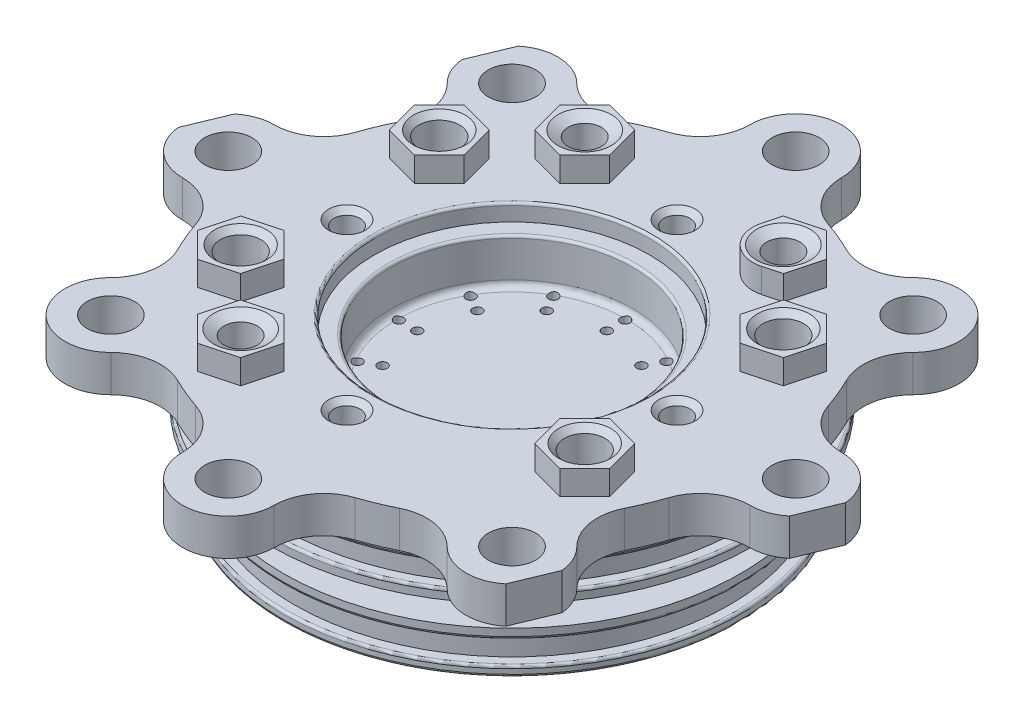
SolidWorks part; units mm, degrees
material "6061-T6 (SS)"
ref_plane "Front Plane" through (0, 0, 0) normal (0, 0, 1) x (1, 0, 0)
ref_plane "Top Plane" through (0, 0, 0) normal (0, 1, 0) x (1, 0, 0)
ref_plane "Right Plane" through (0, 0, 0) normal (1, 0, 0) x (0, 0, -1)
sketch "Sketch1" plane through (0, 0, 0) normal (0, 0, 1) x (1, 0, 0)
  line L0 (0, 2.032) -> (0, 18.8976)
  line L1 (0, 18.8976) -> (25.1206, 18.8976)
  line L2 (25.1206, 18.8976) -> (25.1206, 28.1432)
  line L3 (28.575, 31.5976) -> (69.85, 31.5976)
  line L4 (69.85, 31.5976) -> (69.85, 23.9776)
  line L5 (69.85, 23.9776) -> (50.248, 23.9776)
  line L6 (50.248, 23.9776) -> (50.248, 21.9456)
  line L7 (50.248, 21.9456) -> (47.962, 21.9456)
  line L8 (47.962, 21.9456) -> (47.962, 17.1958)
  line L9 (47.962, 17.1958) -> (50.248, 17.1958)
  line L10 (50.248, 17.1958) -> (50.248, 15.1638)
  line L11 (50.248, 15.1638) -> (38.1, 15.1638)
  line L12 (38.1, 15.1638) -> (38.1, 8.8138)
  line L13 (38.1, 8.8138) -> (47.498, 8.8138)
  line L14 (47.498, 8.8138) -> (47.498, 6.7818)
  line L15 (47.498, 6.7818) -> (45.212, 6.7818)
  line L16 (45.212, 6.7818) -> (45.212, 2.032)
  line L17 (45.212, 2.032) -> (47.498, 2.032)
  line L18 (47.498, 2.032) -> (47.498, 0)
  line L19 (47.498, 0) -> (44.069, 0)
  line L20 (44.069, 0) -> (42.037, 2.032)
  line L21 (42.037, 2.032) -> (0, 2.032)
  line L22 (28.575, 31.5976) -> (28.575, 28.1432)
  line L23 (28.575, 28.1432) -> (25.1206, 28.1432)
  dimension "D1" = 2.032
  dimension "D2" = 2.032
  dimension "D3" = 2.032
  dimension "D4" = 2.032
  dimension "D5" = 2.286
  dimension "D6" = 2.286
  dimension "D7" = 4.7498
  dimension "D8" = 4.7498
  dimension "D9" = 47.498
  dimension "D10" = 6.35
  dimension "D11" = 7.62
  dimension "D12" = 3.4544
  dimension "D13" = 28.575
  dimension "D14" = 45
  dimension "D15" = 3.429
  dimension "D16" = 38.1
  dimension "D17" = 69.85
  dimension "D18" = 50.248
  dimension "D19" = 3.4544
  dimension "D20" = 12.7
revolve "Revolve1" add sketch "Sketch1" angle 360 about L0
fillet "Fillet1" radius 0.508 5 edges at (0, 21.9456, -50.248) (0, 17.1958, -50.248) (0, 6.7818, -47.498) (0, 0, -47.498) (0, 2.032, -47.498)
fillet "Fillet2" radius 0.508 5 edges at (0, 0, -44.069) (0, 2.032, -42.037) (0, 8.8138, -38.1) (0, 15.1638, -38.1) (0, 23.9776, -50.248)
fillet "Fillet3" radius 1.27 1 edges at (0, 18.8976, -25.1206)
fillet "Fillet4" radius 0.508 2 edges at (0, 28.1432, -25.1206) (0, 31.5976, -28.575)
sketch "Sketch3" plane through (0, 0, 0) normal (0, 1, 0) x (1, 0, 0)
  arc A0 (-46.4668, 23.062) -> (-49.1643, 16.5497) centre (0, 0) ccw
  circle A1 centre (0, 0) radius 58.9409 construction
  arc A2 (9.525, 58.9409) -> (-9.525, 58.9409) centre (0, 58.9409) ccw
  circle A3 centre (0, 58.9409) radius 4.9022
  arc A4 (9.525, 58.9409) -> (16.5497, 49.1643) centre (19.8407, 58.9409) ccw
  arc A5 (-9.525, 58.9409) -> (-16.5497, 49.1643) centre (-19.8407, 58.9409) cw
  arc A8 (34.9423, 48.4127) -> (23.062, 46.4668) centre (27.648, 55.707) cw
  arc A9 (48.4127, 34.9423) -> (34.9423, 48.4127) centre (41.6775, 41.6775) ccw
  circle A10 centre (41.6775, 41.6775) radius 4.9022
  arc A11 (48.4127, 34.9423) -> (46.4668, 23.062) centre (55.707, 27.648) ccw
  arc A12 (58.9409, 9.525) -> (49.1643, 16.5497) centre (58.9409, 19.8407) cw
  arc A13 (58.9409, -9.525) -> (58.9409, 9.525) centre (58.9409, 0) ccw
  circle A14 centre (58.9409, 0) radius 4.9022
  arc A15 (58.9409, -9.525) -> (49.1643, -16.5497) centre (58.9409, -19.8407) ccw
  arc A16 (48.4127, -34.9423) -> (46.4668, -23.062) centre (55.707, -27.648) cw
  arc A17 (34.9423, -48.4127) -> (48.4127, -34.9423) centre (41.6775, -41.6775) ccw
  circle A18 centre (41.6775, -41.6775) radius 4.9022
  arc A19 (34.9423, -48.4127) -> (23.062, -46.4668) centre (27.648, -55.707) ccw
  arc A20 (9.525, -58.9409) -> (16.5497, -49.1643) centre (19.8407, -58.9409) cw
  arc A21 (-9.525, -58.9409) -> (9.525, -58.9409) centre (0, -58.9409) ccw
  circle A22 centre (0, -58.9409) radius 4.9022
  arc A23 (-9.525, -58.9409) -> (-16.5497, -49.1643) centre (-19.8407, -58.9409) ccw
  arc A24 (-34.9423, -48.4127) -> (-23.062, -46.4668) centre (-27.648, -55.707) cw
  arc A25 (-48.4127, -34.9423) -> (-34.9423, -48.4127) centre (-41.6775, -41.6775) ccw
  circle A26 centre (-41.6775, -41.6775) radius 4.9022
  arc A27 (-48.4127, -34.9423) -> (-46.4668, -23.062) centre (-55.707, -27.648) ccw
  arc A28 (-58.9409, -9.525) -> (-49.1643, -16.5497) centre (-58.9409, -19.8407) cw
  arc A29 (-58.9409, 9.525) -> (-58.9409, -9.525) centre (-58.9409, 0) ccw
  circle A30 centre (-58.9409, 0) radius 4.9022
  arc A31 (-58.9409, 9.525) -> (-49.1643, 16.5497) centre (-58.9409, 19.8407) ccw
  arc A32 (-48.4127, 34.9423) -> (-46.4668, 23.062) centre (-55.707, 27.648) cw
  arc A33 (-34.9423, 48.4127) -> (-48.4127, 34.9423) centre (-41.6775, 41.6775) ccw
  circle A34 centre (-41.6775, 41.6775) radius 4.9022
  arc A35 (-34.9423, 48.4127) -> (-23.062, 46.4668) centre (-27.648, 55.707) ccw
  arc A36 (-16.5497, 49.1643) -> (-23.062, 46.4668) centre (0, 0) ccw
  arc A37 (23.062, 46.4668) -> (16.5497, 49.1643) centre (0, 0) ccw
  arc A38 (49.1643, 16.5497) -> (46.4668, 23.062) centre (0, 0) ccw
  arc A39 (46.4668, -23.062) -> (49.1643, -16.5497) centre (0, 0) ccw
  arc A40 (16.5497, -49.1643) -> (23.062, -46.4668) centre (0, 0) ccw
  arc A41 (-23.062, -46.4668) -> (-16.5497, -49.1643) centre (0, 0) ccw
  arc A42 (-49.1643, -16.5497) -> (-46.4668, -23.062) centre (0, 0) ccw
  circle A43 centre (0, 0) radius 69.85
  point P70 (0, 0)
  dimension "D1" = 103.75
  dimension "D2" = 117.8818
  dimension "D3" = 9.8044
  dimension "D4" = 19.05
  dimension "D5" = 8
extrude "Cut-Extrude2" cut sketch "Sketch3" along normal through all contours A43 A42 A28 A29 A31 A0 A32 A33 A35 A36 A5 A2 A4 A37 A8 A9 A11 A38 A12 A13 A15 A39 A16 A17 A19 A40 A20 A21 A23 A41 A24 A25 A27 | A14 | A18 | A22 | A10 | A3 | A34 | A30 | A26 region at (0, 0, -58.9409) region at (41.6775, 0, -41.6775) region at (58.9409, 0, 0) region at (41.6775, 0, 41.6775) region at (0, 0, 58.9409) region at (-41.6775, 0, 41.6775) region at (-58.9409, 0, 0) region at (-41.6775, 0, -41.6775) region at (-69.6524, 0, 0)
sketch "Sketch5" plane through (0, 0, 0) normal (0, 1, 0) x (1, 0, 0)
  line L0 (0, 0) -> (80.2299, 0) construction
  line L1 (0, 0) -> (67.4633, -18.0767)
  dimension "D1" = 15
ref_plane "Plane1" through (0, 0, 0) normal (0.9659, 0, 0.2588) x (0.2588, 0, -0.9659)
sketch "Sketch6" plane through (0, 0, 0) normal (0.9659, 0, 0.2588) x (0.2588, 0, -0.9659)
  line L0 (-38.608, 15.1638) -> (38.608, 15.1638) construction
  line L1 (38.608, 8.8138) -> (-38.608, 8.8138) construction
  circle A0 centre (0, 11.9888) radius 3.175
  dimension "D1" = 6.35
extrude "Cut-Extrude3" cut sketch "Sketch6" against normal through all both and the other way through all
pattern_circular "CirPattern1" count 12 over 360 of "Cut-Extrude3"
sketch "Sketch8" plane through (0, 0, 0) normal (0, 1, 0) x (1, 0, 0)
  circle A0 centre (0, 0) radius 21.59 construction
  circle A1 centre (0, 0) radius 19.685 construction
  circle A2 centre (0, 0) radius 23.495 construction
  circle A3 centre (0, 19.685) radius 0.9922
  circle A4 centre (0, 23.495) radius 0.9922
  circle A5 centre (11.7475, 20.3473) radius 0.9922
  circle A6 centre (9.8425, 17.0477) radius 0.9922
  circle A7 centre (20.3473, 11.7475) radius 0.9922
  circle A8 centre (17.0477, 9.8425) radius 0.9922
  circle A9 centre (23.495, 0) radius 0.9922
  circle A10 centre (19.685, 0) radius 0.9922
  circle A11 centre (20.3473, -11.7475) radius 0.9922
  circle A12 centre (17.0477, -9.8425) radius 0.9922
  circle A13 centre (11.7475, -20.3473) radius 0.9922
  circle A14 centre (9.8425, -17.0477) radius 0.9922
  circle A15 centre (0, -23.495) radius 0.9922
  circle A16 centre (0, -19.685) radius 0.9922
  circle A17 centre (-11.7475, -20.3473) radius 0.9922
  circle A18 centre (-9.8425, -17.0477) radius 0.9922
  circle A19 centre (-20.3473, -11.7475) radius 0.9922
  circle A20 centre (-17.0477, -9.8425) radius 0.9922
  circle A21 centre (-23.495, 0) radius 0.9922
  circle A22 centre (-19.685, 0) radius 0.9922
  circle A23 centre (-20.3473, 11.7475) radius 0.9922
  circle A24 centre (-17.0477, 9.8425) radius 0.9922
  circle A25 centre (-11.7475, 20.3473) radius 0.9922
  circle A26 centre (-9.8425, 17.0477) radius 0.9922
  point P56 (0, 0)
  dimension "D1" = 43.18
  dimension "D2" = 1.905
  dimension "D3" = 1.905
  dimension "D4" = 1.9844
  dimension "D5" = 12
extrude "5/64 - 24 holes" cut sketch "Sketch8" against normal through all both and the other way through all
sketch "Sketch9" plane through (0, 0, 0) normal (0, 0, 1) x (1, 0, 0)
  line L0 (19.685, 2.032) -> (19.685, 11.7387)
  line L1 (23.495, 2.032) -> (23.495, 11.7387)
  line L2 (18.6928, 2.032) -> (20.6772, 2.032) construction
  line L3 (22.5028, 2.032) -> (24.4872, 2.032) construction
  line L4 (41.933, 12.85) -> (31.115, 2.032)
  line L5 (3.4695, 10.6275) -> (12.065, 2.032)
  line L6 (46.99, 2.032) -> (-46.99, 2.032) construction
  dimension "D1" = 45
  dimension "D2" = 45
  dimension "D3" = 7.62
  dimension "D4" = 7.62
ref_plane "Plane2" through (41.933, 12.85, 0) normal (-0.7071, -0.7071, 0) x (-0.7071, 0.7071, 0)
sketch "Sketch10" plane through (41.933, 12.85, 0) normal (-0.7071, -0.7071, 0) x (-0.7071, 0.7071, 0)
  circle A0 centre (0, 0) radius 0.7556
  dimension "D1" = 1.5113
ref_plane "Plane3" through (3.4695, 10.6275, 0) normal (0.7071, -0.7071, 0) x (0, 0, -1)
sketch "Sketch11" plane through (3.4695, 10.6275, 0) normal (0.7071, -0.7071, 0) x (0, 0, -1)
  circle A0 centre (0, 0) radius 0.7556
  dimension "D1" = 1.5113
extrude "#53 - 12 holes" cut sketch "Sketch10" along normal through all
extrude "Cut-Extrude6" cut sketch "Sketch11" along normal through all
pattern_circular "CirPattern2" count 12 over 360 about axis through (0, 8.8138, 0) along (0, -1, 0) of "#53 - 12 holes", "Cut-Extrude6"
sketch "Sketch12" plane through (0, 0, 0) normal (0, 0, 1) x (1, 0, 0)
  line L0 (40.4319, 11.6683) -> (41.275, 2.032)
  line L1 (41.275, 2.032) -> (41.275, 15.9877) construction
  line L2 (5.1877, 2.032) -> (6.8773, 2.032) construction
  dimension "D1" = 5
  dimension "D2" = 41.275
ref_plane "Plane4" through (40.4319, 11.6683, 0) normal (0.0872, -0.9962, 0) x (-0.9962, -0.0872, 0)
sketch "Sketch13" plane through (40.4319, 11.6683, 0) normal (0.0872, -0.9962, 0) x (-0.9962, -0.0872, 0)
  circle A0 centre (0, 0) radius 0.2667
  dimension "D1" = 0.5334
extrude "#75 - 36 holes" cut sketch "Sketch13" along normal through all
pattern_circular "CirPattern3" count 36 over 360 about axis through (0, 15.1638, 0) along (0, -1, 0) of "#75 - 36 holes"
sketch "Sketch14" plane through (0, 0, 0) normal (0, 1, 0) x (1, 0, 0)
  circle A0 centre (0, 0) radius 0.2667
  dimension "D1" = 0.5334
extrude "Cut-Extrude8" cut sketch "Sketch14" along normal blind 10.16
sketch "Sketch15" plane through (0, 0, 0) normal (0, 1, 0) x (1, 0, 0)
  line L0 (0, 0) -> (0, 41.275) construction
  line L1 (0, 0) -> (35.7452, 20.6375) construction
  line L2 (0, 0) -> (35.7452, -20.6375) construction
  line L3 (0, 0) -> (0, -41.275) construction
  line L4 (0, 0) -> (-35.7452, -20.6375) construction
  line L5 (0, 0) -> (-35.7452, 20.6375) construction
  point P5 (35.7452, 20.6375)
  point P6 (35.7452, -20.6375)
  point P8 (-35.7452, -20.6375)
  point P9 (-35.7452, 20.6375)
  point P10 (0, 0)
  point P19 (35.7452, 20.6375)
  point P23 (-35.7452, 20.6375)
  point P25 (-35.7452, -20.6375)
  point P27 (35.7452, -20.6375)
  dimension "D1" = 6
  dimension "D2" = 41.275
sketch "Sketch40" plane through (0, 31.5976, 0) normal (0, 1, 0) x (1, 0, 0)
  line L0 (0, 0) -> (-12.565, 0) construction
  line L7 (-30.5604, 25.8223) -> (-37.6429, 27.72)
  line L8 (-37.6429, 27.72) -> (-42.8277, 22.5353)
  line L9 (-42.8277, 22.5353) -> (-40.93, 15.4527)
  line L10 (-40.93, 15.4527) -> (-33.8474, 13.555)
  line L11 (-33.8474, 13.555) -> (-28.6627, 18.7397)
  line L12 (-28.6627, 18.7397) -> (-30.5604, 25.8223)
  line L14 (-33.8474, -13.555) -> (-40.93, -15.4527)
  line L15 (-40.93, -15.4527) -> (-42.8277, -22.5353)
  line L16 (-42.8277, -22.5353) -> (-37.6429, -27.72)
  line L17 (-37.6429, -27.72) -> (-30.5604, -25.8223)
  line L18 (-30.5604, -25.8223) -> (-28.6627, -18.7397)
  line L19 (-28.6627, -18.7397) -> (-33.8474, -13.555)
  line L20 (40.93, -15.4527) -> (33.8474, -13.555)
  line L21 (33.8474, -13.555) -> (28.6627, -18.7397)
  line L22 (28.6627, -18.7397) -> (30.5604, -25.8223)
  line L23 (30.5604, -25.8223) -> (37.6429, -27.72)
  line L24 (37.6429, -27.72) -> (42.8277, -22.5353)
  line L25 (42.8277, -22.5353) -> (40.93, -15.4527)
  line L26 (37.6429, 27.72) -> (30.5604, 25.8223)
  line L27 (30.5604, 25.8223) -> (28.6627, 18.7397)
  line L28 (28.6627, 18.7397) -> (33.8474, 13.555)
  line L29 (33.8474, 13.555) -> (40.93, 15.4527)
  line L30 (40.93, 15.4527) -> (42.8277, 22.5353)
  line L31 (42.8277, 22.5353) -> (37.6429, 27.72)
  circle A0 centre (-35.7452, 20.6375) radius 6.35 construction
  circle A1 centre (-35.7452, -20.6375) radius 6.35 construction
  circle A2 centre (35.7452, -20.6375) radius 6.35 construction
  circle A3 centre (35.7452, 20.6375) radius 6.35 construction
  dimension "D3" = 12.7
  dimension "D4" = 12.7
  dimension "D5" = 12.7
  dimension "D1" = 12.7
  dimension "D2" = 45
  dimension "D6" = 45
  dimension "D7" = 45
  dimension "D8" = 45
extrude "Boss-Extrude4" add sketch "Sketch40" along normal blind 5.08
sketch "Sketch19" plane through (0, 36.6776, 0) normal (0, 1, 0) x (1, 0, 0)
  point P0 (35.7452, -20.6375)
  point P2 (35.7452, 20.6375)
  point P4 (-35.7452, 20.6375)
  point P6 (-35.7452, -20.6375)
hole_wizard "3/8-24 Tapped Hole1" positions "Sketch19" profile "Sketch39" tap size "3/8-24" standard "ANSI Inch"
sketch "Sketch39" plane through (35.7452, 36.6776, 20.6375) normal (1, 0, 0) x (0, 0, 1)
  line L0 (0, 0) -> (0, 18.5355)
  line L1 (0, 18.5355) -> (4.2164, 16.002)
  line L2 (4.2164, 16.002) -> (4.2164, 1.1811)
  line L3 (4.2164, 1.1811) -> (5.3975, 0)
  line L5 (5.3975, 0) -> (0, 0)
  line L6 (-4.2164, 1.1811) -> (-5.3975, 0) construction
  line L10 (0, 18.5355) -> (-4.2164, 16.002) construction
  line L11 (0, -6.35) -> (0, 107.95) construction
  dimension "Tap Drill Dia." = 8.4328
  dimension "Tap Drill Depth" = 16.002
  dimension "Near C'Sink Dia." = 10.795
  dimension "Near C'Sink Angle" = 90
  dimension "Drill Angle" = 118
cosmetic thread "Hole Thread24" parameters "D1"=12.7, "D2"=9.525
cosmetic thread "Hole Thread25" parameters "D1"=12.7, "D2"=9.525
cosmetic thread "Hole Thread26" parameters "D1"=12.7, "D2"=9.525
cosmetic thread "Hole Thread27" parameters "D1"=12.7, "D2"=9.525
sketch "Sketch37" plane through (0, 31.5976, 0) normal (0, 1, 0) x (1, 0, 0)
  point P0 (0, 34.29)
  point P3 (34.29, 0)
  point P6 (0, -34.29)
  point P7 (-34.29, 0)
  dimension "D1" = 34.29
  dimension "D2" = 4
hole_wizard "1/4-28 Tapped Hole3" positions "Sketch37" profile "Sketch38" tap size "1/4-28" standard "ANSI Inch"
sketch "Sketch38" plane through (0, 31.5976, -34.29) normal (1, 0, 0) x (0, 0, 1)
  line L0 (0, 0) -> (0, 12.0394)
  line L1 (0, 12.0394) -> (2.7051, 10.414)
  line L2 (2.7051, 10.414) -> (2.7051, 1.1049)
  line L3 (2.7051, 1.1049) -> (3.81, 0)
  line L5 (3.81, 0) -> (0, 0)
  line L6 (-2.7051, 1.1049) -> (-3.81, 0) construction
  line L10 (0, 12.0394) -> (-2.7051, 10.414) construction
  line L11 (0, -6.35) -> (0, 107.95) construction
  dimension "Tap Drill Dia." = 5.4102
  dimension "Tap Drill Depth" = 10.414
  dimension "Near C'Sink Dia." = 7.62
  dimension "Near C'Sink Angle" = 90
  dimension "Drill Angle" = 118
cosmetic thread "Hole Thread20" parameters "D1"=7.62, "D2"=6.35
cosmetic thread "Hole Thread21" parameters "D1"=7.62, "D2"=6.35
cosmetic thread "Hole Thread22" parameters "D1"=7.62, "D2"=6.35
cosmetic thread "Hole Thread23" parameters "D1"=7.62, "D2"=6.35
sketch "Sketch25" plane through (0, 0, 0) normal (0, 1, 0) x (1, 0, 0)
  line L0 (0, 0) -> (-44.45, 0) construction
  line L1 (0, 0) -> (-22.225, 38.4948) construction
  line L2 (0, 0) -> (18.415, 31.8957) construction
  line L3 (0, 0) -> (44.45, 0) construction
  line L4 (0, 0) -> (22.225, -38.4948) construction
  line L5 (0, 0) -> (-22.225, -38.4948) construction
  line L6 (18.415, 31.8957) -> (19.685, 34.0954) construction
  point P11 (0, 0)
  dimension "D2" = 44.45
  dimension "D1" = 36.83
  dimension "D3" = 39.37
sketch "Sketch27" plane through (0, 0, 0) normal (0, 1, 0) x (1, 0, 0)
  line L0 (0, 0) -> (-43.8172, 0) construction
  line L1 (-22.5353, 42.8277) -> (-27.72, 37.6429)
  line L2 (-27.72, 37.6429) -> (-25.8223, 30.5604)
  line L3 (-25.8223, 30.5604) -> (-18.7397, 28.6627)
  line L4 (-18.7397, 28.6627) -> (-13.555, 33.8474)
  line L5 (-13.555, 33.8474) -> (-15.4527, 40.93)
  line L6 (-15.4527, 40.93) -> (-22.5353, 42.8277)
  line L7 (0, 0) -> (-22.225, 38.4948) construction
  line L8 (27.72, 37.6429) -> (22.5353, 42.8277)
  line L9 (22.5353, 42.8277) -> (15.4527, 40.93)
  line L10 (15.4527, 40.93) -> (14.5039, 37.3887)
  line L12 (22.281, 29.6116) -> (25.8223, 30.5604)
  line L13 (25.8223, 30.5604) -> (27.72, 37.6429)
  line L14 (17.3095, 30.0929) -> (19.9019, 27.5006) [skipped]
  line L15 (-13.555, -33.8474) -> (-18.7397, -28.6627)
  line L16 (-18.7397, -28.6627) -> (-25.8223, -30.5604)
  line L17 (-25.8223, -30.5604) -> (-27.72, -37.6429)
  line L18 (-27.72, -37.6429) -> (-22.5353, -42.8277)
  line L19 (-22.5353, -42.8277) -> (-15.4527, -40.93)
  line L20 (-15.4527, -40.93) -> (-13.555, -33.8474)
  line L21 (0, 0) -> (-22.225, -38.4948) construction
  line L22 (0, 0) -> (18.415, 31.8957) construction
  line L23 (-33.8474, 13.555) -> (-28.6627, 18.7397) construction
  line L24 (-28.6627, -18.7397) -> (-33.8474, -13.555) construction
  line L25 (42.8277, 22.5353) -> (37.6429, 27.72) construction
  circle A0 centre (-20.6375, 35.7452) radius 6.35 construction
  arc A1 (14.5039, 37.3887) -> (22.281, 29.6116) centre (20.6375, 35.7452) ccw
  circle A2 centre (-20.6375, -35.7452) radius 6.35 construction
  dimension "D1" = 12.7
extrude "Boss-Extrude3" add sketch "Sketch27" along normal blind 5.08 from surface starting at face at (0, 31.5976, -30.48)
sketch "Sketch28" plane through (0, 36.6776, 0) normal (0, 1, 0) x (1, 0, 0)
  point P0 (-20.6375, -35.7452)
  point P2 (-20.6375, 35.7452)
  point P4 (20.6375, 35.7452)
hole_wizard "5/16-24 Tapped Hole1" positions "Sketch28" profile "Sketch29" tap size "5/16-24" standard "ANSI Inch"
sketch "Sketch29" plane through (-20.6375, 36.6776, 35.7452) normal (1, 0, 0) x (0, 0, 1)
  line L0 (0, 0) -> (0, 14.7756)
  line L1 (0, 14.7756) -> (3.4544, 12.7)
  line L2 (3.4544, 12.7) -> (3.4544, 0)
  line L5 (3.4544, 0) -> (0, 0)
  line L10 (0, 14.7756) -> (-3.4544, 12.7) construction
  line L11 (0, -6.35) -> (0, 107.95) construction
  dimension "Tap Drill Dia." = 6.9088
  dimension "Tap Drill Depth" = 12.7
  dimension "Drill Angle" = 118
chamfer "Chamfer1" distance 2.1082 angle 30 3 edges at (-20.6375, 36.6776, 39.1996) (20.6375, 36.6776, -32.2908) (-20.6375, 36.6776, -32.2908) first distance on face at (-20.6375, 36.6776, 35.7452) first distance on face at (20.6375, 36.6776, -32.2908) first distance on face at (-20.6375, 36.6776, -32.2908)
sketch "Sketch30" plane through (0, 31.5976, 0) normal (0, 1, 0) x (1, 0, 0)
  circle A0 centre (-20.6375, 35.7452) radius 0.7937
  circle A1 centre (-20.6375, -35.7452) radius 0.7937
  dimension "D1" = 1.5875
extrude "Cut-Extrude9" cut sketch "Sketch30" against normal up to surface (16.4338 mm away) up to face at (0, 15.1638, 0)
ref_plane "Plane5" through (0, 0, 0) normal (0.866, 0, 0.5) x (0.5, 0, -0.866)
sketch "Sketch32" plane through (0, 0, 0) normal (0.866, 0, 0.5) x (0.5, 0, -0.866)
  line L0 (27.94, 2.032) -> (38.2188, 24.0751)
  line L1 (27.94, 2.032) -> (27.94, 24.1362) construction
  line L2 (-0.2667, 2.032) -> (0.2667, 2.032) construction
  dimension "D1" = 27.94
  dimension "D2" = 25
ref_plane "Plane6" through (19.1094, 24.0751, -33.0985) normal (-0.2113, -0.9063, 0.366) x (-0.9774, 0.1959, -0.0791)
sketch "Sketch33" plane through (19.1094, 24.0751, -33.0985) normal (-0.2113, -0.9063, 0.366) x (-0.9774, 0.1959, -0.0791)
  circle A0 centre (0, 0) radius 0.7937
  dimension "D1" = 1.5875
extrude "Cut-Extrude11" cut sketch "Sketch33" along normal through all
sketch "Sketch41" plane through (0, 0, 0) normal (0, 1, 0) x (1, 0, 0)
  line L0 (-44.45, 0) -> (0, 44.45)
  line L3 (0, 44.45) -> (44.45, 0)
  line L4 (44.45, 0) -> (0, -44.45)
  line L5 (0, -44.45) -> (-44.45, 0)
  circle A12 centre (0, 35.56) radius 3.175
  circle A13 centre (-35.56, 0) radius 3.175
  circle A14 centre (35.56, 0) radius 3.175
  circle A15 centre (0, -35.56) radius 3.175
  circle A16 centre (0, 0) radius 44.45
  circle A29 centre (0, 0) radius 31.75 construction
  point P33 (0, 0)
  dimension "D1" = 6.35
sketch "Sketch42" plane through (0, 0, 0) normal (0, 1, 0) x (1, 0, 0)
  line L0 (-73.776, -13.8368) -> (-44.0261, 57.9857)
  line L1 (0, 0) -> (-58.0797, 24.0574) construction
  line L2 (0, 0) -> (-14.4415, 0) construction
  line L3 (-44.0261, 57.9857) -> (-58.1836, 63.8499)
  line L4 (-58.1836, 63.8499) -> (-87.9334, -7.9726)
  line L5 (-87.9334, -7.9726) -> (-73.776, -13.8368)
  line L6 (73.776, 13.8368) -> (44.0261, -57.9857)
  line L7 (44.0261, -57.9857) -> (58.1836, -63.8499)
  line L8 (58.1836, -63.8499) -> (87.9334, 7.9726)
  line L9 (87.9334, 7.9726) -> (73.776, 13.8368)
  point P14 (0, 0)
  dimension "D1" = 22.5
  dimension "D2" = 62.865
  dimension "D3" = 2
extrude "Cut-Extrude12" cut sketch "Sketch42" against normal through all both and the other way through all
